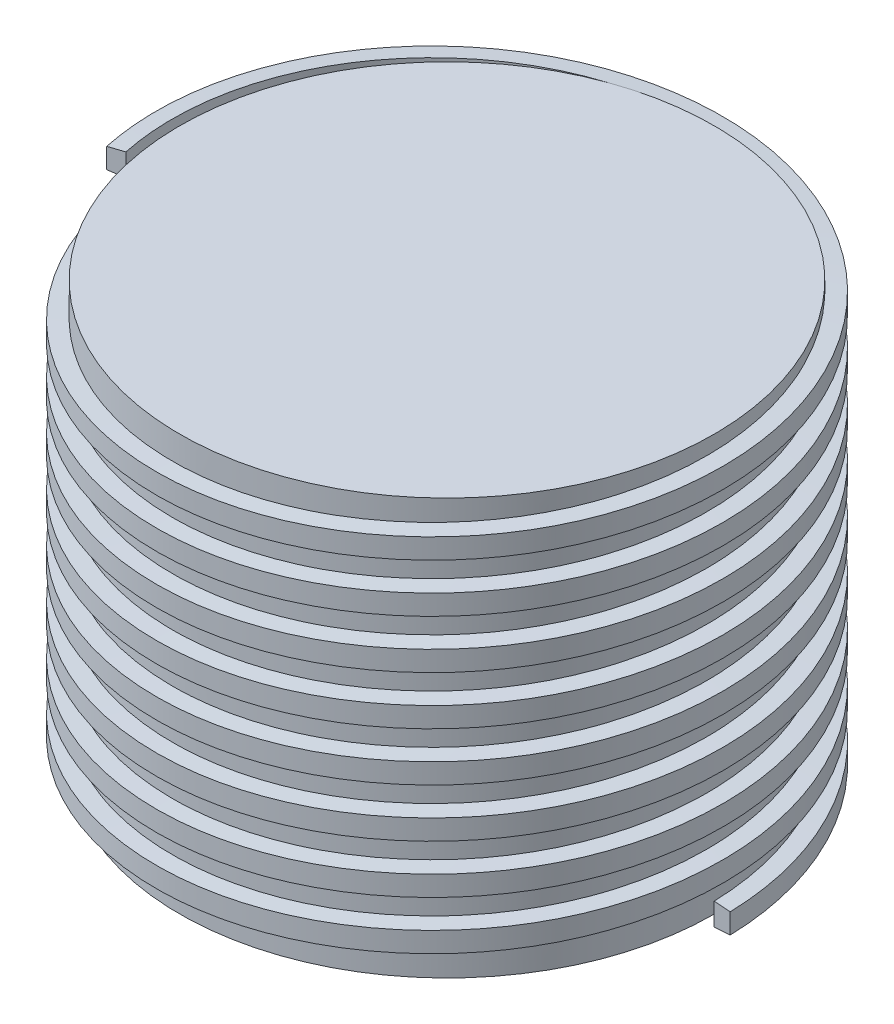
SolidWorks part; units mm, degrees
ref_plane "Front Plane" through (0, 0, 0) normal (0, 0, 1) x (1, 0, 0)
ref_plane "Top Plane" through (0, 0, 0) normal (0, 1, 0) x (1, 0, 0)
ref_plane "Right Plane" through (0, 0, 0) normal (1, 0, 0) x (0, 0, -1)
sketch "Sketch1" plane through (0, 0, 0) normal (0, 1, 0) x (1, 0, 0)
  circle A0 centre (0, 0) radius 4.5
  dimension "D1" = 9
extrude "Boss-Extrude1" add sketch "Sketch1" along normal blind 7 contours A0
sketch "Sketch2" plane through (0, 0, 0) normal (0, 0, 1) x (1, 0, 0)
  line L0 (4.5, 0) -> (4.77, 0) construction
  line L1 (4.77, -0.17) -> (4.77, 0.17)
  line L2 (4.77, 0.17) -> (4.5, 0.19)
  line L3 (4.5, 0) -> (4.5, 7) construction
  line L4 (4.5, 0.19) -> (4.5, -0.19)
  line L5 (4.77, -0.17) -> (4.5, -0.19)
  dimension "D1" = 4.77
  dimension "D2" = 0.34
  dimension "D3" = 0.38
sketch "Sketch5" plane through (0, 0, 0) normal (0, 1, 0) x (1, 0, 0)
  circle A0 centre (0, 0) radius 4.5 construction
  circle A1 centre (0, 0) radius 4.5
curve "Helix/Spiral1" pitch 0.82 height 7 radius 4.5 centre (0, 0, 0) axis (0, 1, 0) start towards (1, 0, 0)
sweep "Sweep1" add profiles "Sketch2" path "Helix/Spiral1"
